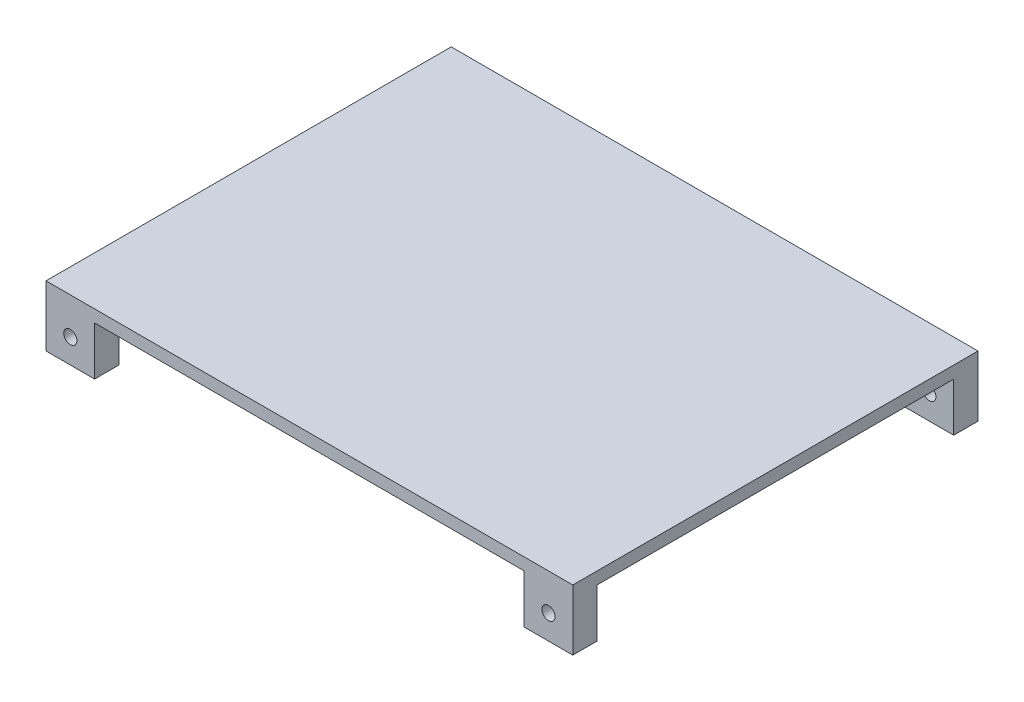
SolidWorks part; units mm, degrees
ref_plane "Front Plane" through (0, 0, 0) normal (0, 0, 1) x (1, 0, 0)
ref_plane "Top Plane" through (0, 0, 0) normal (0, 1, 0) x (1, 0, 0)
ref_plane "Right Plane" through (0, 0, 0) normal (1, 0, 0) x (0, 0, -1)
sketch "Sketch1" plane through (0, 0, 0) normal (0, 1, 0) x (1, 0, 0)
  line L1 (0, 0) -> (130, 0)
  line L2 (0, 0) -> (0, 100)
  line L3 (0, 100) -> (130, 100)
  line L4 (130, 0) -> (130, 100)
  dimension "D1" = 130
  dimension "D2" = 100
extrude "Boss-Extrude1" add sketch "Sketch1" along normal blind 3
sketch "Sketch2" plane through (0, 0, 0) normal (0, -1, 0) x (1, 0, 0)
  line L0 (65, 0) -> (65, -100) construction
  line L1 (0, 0) -> (12, 0)
  line L2 (0, 0) -> (0, -6)
  line L3 (0, -6) -> (12, -6)
  line L4 (12, 0) -> (12, -6)
  line L5 (0, 0) -> (130, 0) construction
  line L6 (130, -100) -> (0, -100) construction
  line L7 (130, -6) -> (118, -6)
  line L8 (118, 0) -> (118, -6)
  line L9 (130, 0) -> (118, 0)
  line L10 (130, 0) -> (130, -6)
  line L11 (0, -50) -> (130, -50) construction
  line L12 (0, -100) -> (0, 0) construction
  line L13 (130, 0) -> (130, -100) construction
  line L14 (130, -100) -> (130, -94)
  line L15 (130, -100) -> (118, -100)
  line L16 (118, -100) -> (118, -94)
  line L17 (130, -94) -> (118, -94)
  line L18 (0, -94) -> (12, -94)
  line L19 (12, -100) -> (12, -94)
  line L20 (0, -100) -> (12, -100)
  line L21 (0, -100) -> (0, -94)
  dimension "D1" = 6
  dimension "D2" = 12
extrude "Boss-Extrude2" add sketch "Sketch2" along normal blind 12
sketch "Sketch4" plane through (0, 0, 0) normal (0, 0, 1) x (1, 0, 0)
  line L0 (12, -12) -> (12, 0) construction
  line L1 (12, -12) -> (0, -12) construction
  line L2 (65, 3) -> (65, 0) construction
  line L3 (0, 3) -> (130, 3) construction
  line L4 (12, 0) -> (118, 0) construction
  circle A0 centre (6, -6) radius 1.625
  circle A1 centre (124, -6) radius 1.625
  dimension "D1" = 3.25
  dimension "D2" = 6
  dimension "D3" = 6
extrude "Cut-Extrude1" cut sketch "Sketch4" against normal through all
